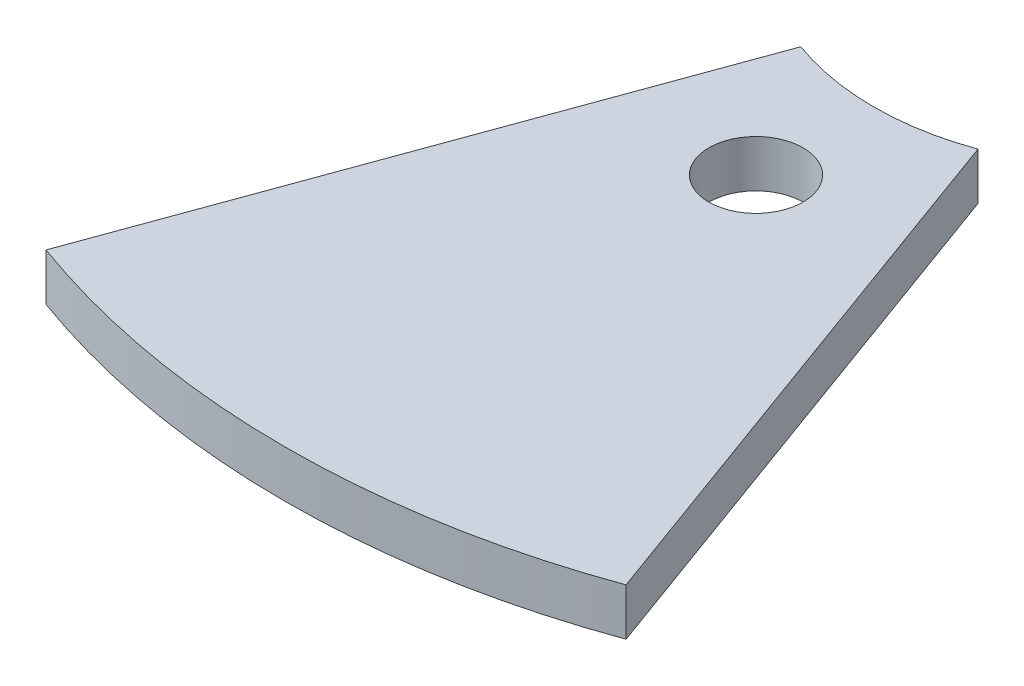
SolidWorks part; units mm, degrees
ref_plane "Front Plane" through (0, 0, 0) normal (0, 0, 1) x (1, 0, 0)
ref_plane "Top Plane" through (0, 0, 0) normal (0, 1, 0) x (1, 0, 0)
ref_plane "Right Plane" through (0, 0, 0) normal (1, 0, 0) x (0, 0, -1)
sketch "Sketch1" plane through (0, 0, 0) normal (0, 1, 0) x (1, 0, 0)
  line L0 (0, 50.8) -> (-39.0929, -56.6069)
  line L1 (0, 50.8) -> (0, 0) construction
  line L2 (0, 50.8) -> (39.0929, -56.6069)
  circle A0 centre (0, 0) radius 6.35
  circle A1 centre (0, 50.8) radius 114.3
  circle A2 centre (0, 50.8) radius 34.925
  point P3 (0, 50.8)
  dimension "D1" = 20
  dimension "D3" = 69.85
  dimension "D4" = 228.6
  dimension "D2" = 50.8
extrude "Boss-Extrude1" add sketch "Sketch1" along normal blind 6.35 contours A2 L0 A1 L2 A0 region at (0, 0, 30.1242)
